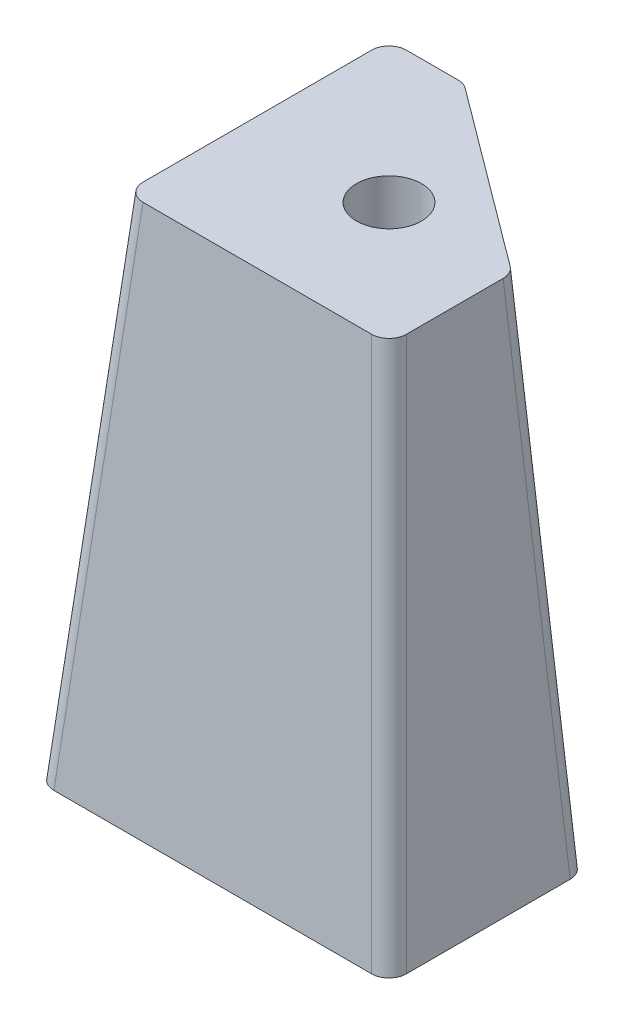
SolidWorks part; units mm, degrees
ref_plane "Front Plane" through (0, 0, 0) normal (0, 0, 1) x (1, 0, 0)
ref_plane "Top Plane" through (0, 0, 0) normal (0, 1, 0) x (1, 0, 0)
ref_plane "Right Plane" through (0, 0, 0) normal (1, 0, 0) x (0, 0, -1)
sketch "Sketch1" plane through (0, 0, 0) normal (0, 1, 0) x (1, 0, 0)
  line L3 (10.4204, -7.2013) -> (-4.5796, -7.2013)
  line L5 (-4.5796, -7.2013) -> (-4.5796, 7.7987)
  line L6 (-4.5796, 7.7987) -> (-0.3125, 7.7987)
  line L7 (-0.3125, 7.7987) -> (10.4204, -0.2013)
  line L8 (10.4204, -0.2013) -> (10.4204, -7.2013)
  dimension "D1" = 15
  dimension "D2" = 15
  dimension "D3" = 7
  dimension "D4" = 126.7
extrude "Boss-Extrude1" add sketch "Sketch1" along normal blind 29
sketch "Sketch2" plane through (0, 0, 0) normal (0, -1, 0) x (1, 0, 0)
  line L1 (10.4204, 7.2013) -> (10.4204, 0.2013) construction
  line L2 (-4.5796, 7.2013) -> (10.4204, 7.2013) construction
  line L3 (-4.5796, -7.7987) -> (-4.5796, 7.2013) construction
  circle A0 centre (-0.5796, 2.2013) radius 2
  circle A1 centre (7.4204, 2.2013) radius 1.5
  dimension "D1" = 4
  dimension "D3" = 3
  dimension "D2" = 4
  dimension "D4" = 3
  dimension "D5" = 5
  dimension "D6" = 5
extrude "Cut-Extrude1" cut sketch "Sketch2" against normal blind 10
sketch "Sketch3" plane through (0, 29, 0) normal (0, 1, 0) x (1, 0, 0)
  line L0 (10.4204, -7.2013) -> (10.4204, -0.2013) construction
  line L1 (-4.5796, -7.2013) -> (10.4204, -7.2013) construction
  circle A0 centre (3.4204, -0.2013) radius 1.85
  dimension "D1" = 3.7
  dimension "D2" = 7
  dimension "D3" = 7
extrude "Cut-Extrude2" cut sketch "Sketch3" against normal blind 12
draft "Draft1" type of draft neutral plane draft angle 5 faces to draft 5 face at (5.0539, 14.5, -3.7987) face at (-2.4461, 14.5, -7.7987) face at (-4.5796, 14.5, -0.2987) face at (10.4204, 14.5, 3.7013) face at (2.9204, 14.5, 7.2013) neutral plane through (0, 29, 0) neutral plane normal (0, 1, 0) parameters "D1"=5
fillet "Fillet1" radius 1 5 edges at (-5.8482, 14.5, 8.4699) (11.6889, 14.5, 8.4699) (-5.8482, 14.5, -9.0673) (0.1083, 14.5, -9.0673) (11.6889, 14.5, -0.4353)
